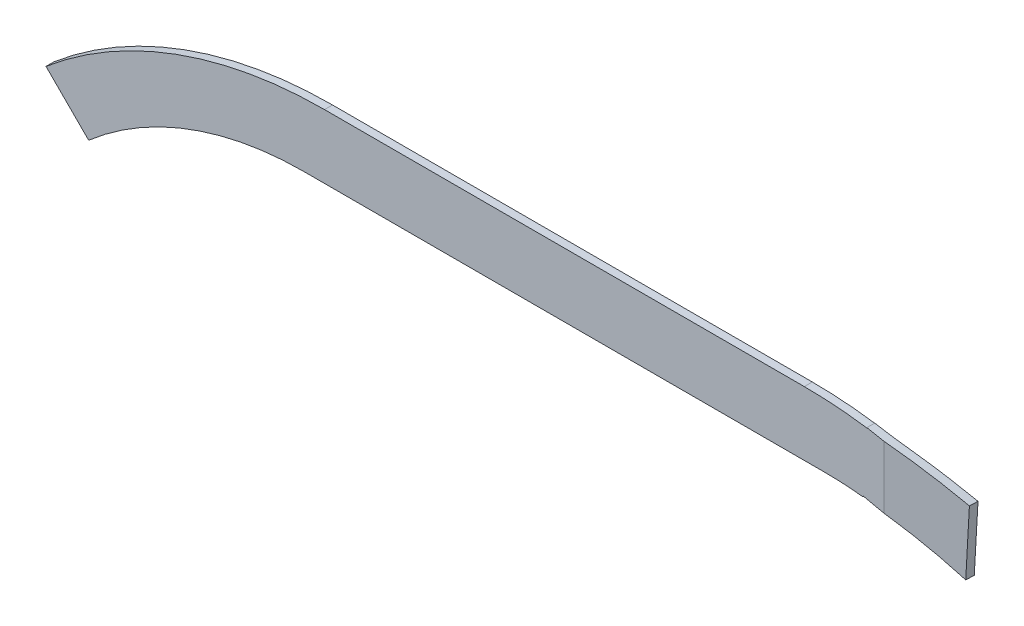
SolidWorks part; units mm, degrees
material "ABS PC"
ref_plane "Front Plane" through (0, 0, 0) normal (0, 0, 1) x (1, 0, 0)
ref_plane "Top Plane" through (0, 0, 0) normal (0, 1, 0) x (1, 0, 0)
ref_plane "Right Plane" through (0, 0, 0) normal (1, 0, 0) x (0, 0, -1)
sketch "Sketch10" plane through (0, 0, 0) normal (0, 0, 1) x (1, 0, 0)
  line L0 (37.4166, 15) -> (102.5834, 15)
  line L1 (70, -22.3542) -> (70, 54.9166) construction
  line L2 (100, 25) -> (40, 25)
  circle A0 centre (0, 0) radius 1.5
  arc A1 (4.1574, -2.7778) -> (37.4166, 15) centre (37.4166, -25) cw
  arc A2 (-4, 3) -> (40, 25) centre (40, -30) cw
  arc A3 (-4, 3) -> (4.1574, -2.7778) centre (0, 0) ccw
  arc A4 (144, 3) -> (135.8426, -2.7778) centre (140, 0) cw
  arc A5 (144, 3) -> (100, 25) centre (100, -30) ccw
  arc A6 (135.8426, -2.7778) -> (102.5834, 15) centre (102.5834, -25) ccw
  circle A7 centre (140, 0) radius 1.5
  point P8 (70, 15)
  point P21 (70, 25)
  dimension "D2" = 3
  dimension "D3" = 10
  dimension "D4" = 10
  dimension "D5" = 55
  dimension "D1" = 40
  dimension "D6" = 15
  dimension "D7" = 70
extrude "Boss-Extrude2" add sketch "Sketch10" along normal blind 18
sketch "Sketch12" plane through (0, 0, 0) normal (0, 1, 0) x (1, 0, 0)
  line L0 (-5, 0) -> (-5, -18) construction
  line L2 (-5, -6) -> (-5, -14)
  line L3 (-5, -6) -> (107.8057, -6)
  line L4 (112.2288, -5.7547) -> (125.7953, -4.2453)
  line L5 (130.2184, -4) -> (145, -4)
  line L6 (145, -18) -> (145, 0) construction
  line L7 (145, -4) -> (145, -8)
  line L8 (145, -18) -> (133.2661, -18)
  line L9 (122.9133, -16.637) -> (118.1585, -15.363)
  line L10 (107.8057, -14) -> (-5, -14)
  line L11 (100, -18) -> (144, -18) construction
  line L12 (145, -10) -> (-10.875, -10) construction
  line L16 (144, 0) -> (100, 0) construction
  line L17 (145, -8) -> (130, -8)
  line L19 (130, -14) -> (145, -14)
  line L21 (130, -8) -> (127.3597, -8.2938)
  line L23 (145, -14) -> (145, -18)
  line L27 (130, -14) -> (126.9891, -13.1932)
  arc A0 (125.7953, -4.2453) -> (130.2184, -4) centre (130.2184, -44) cw
  arc A1 (133.2661, -18) -> (122.9133, -16.637) centre (133.2661, 22) cw
  arc A2 (118.1585, -15.363) -> (107.8057, -14) centre (107.8057, -54) ccw
  arc A3 (107.8057, -6) -> (112.2288, -5.7547) centre (107.8057, 34) ccw
  circle A8 centre (76.008, -10.9313) radius 101.3633
  arc A10 (126.9891, -13.1932) -> (127.3597, -8.2938) centre (127.6362, -10.7784) cw
  point P7 (-5, -10)
  point P27 (128, -4)
  point P30 (128, -18)
  point P36 (110.024, -6)
  dimension "D10" = 40
  dimension "D18" = 2.5
  dimension "D20" = 40
  dimension "D4" = 40
  dimension "D2" = 8
  dimension "D3" = 15
  dimension "D5" = 17
  dimension "D6" = 17
  dimension "D7" = 4
  dimension "D8" = 8
  dimension "D13" = 4
  dimension "D14" = 4
  dimension "D16" = 15
  dimension "D19" = 15
extrude "Cut-Extrude1" cut sketch "Sketch12" against normal blind 21 and the other way blind 53
sketch "Sketch14" plane through (0, 0, 6) normal (0, 0, -1) x (-1, 0, 0)
  line L0 (-102.5834, 16) -> (-37.4166, 16)
  line L1 (-40, 24) -> (-100, 24)
  line L3 (-107.8191, 15.6643) -> (-107.8191, -18.7663)
  line L4 (-107.8191, 35.1683) -> (17.1624, 35.1683)
  line L5 (-107.8191, 35.1683) -> (-107.8191, 23.4309)
  line L9 (-9.7552, 5.263) -> (-4.4079, 10.6104)
  line L10 (-107.8191, -18.7663) -> (17.1624, -18.7663)
  line L11 (17.1624, 35.1683) -> (17.1624, -18.7663)
  arc A0 (-9.7552, 5.263) -> (-37.4166, 16) centre (-37.4166, -25) ccw
  arc A2 (-4.4079, 10.6104) -> (-40, 24) centre (-40, -30) ccw
  arc A3 (-100, 24) -> (-107.8191, 23.4309) centre (-100, -30) ccw
  arc A4 (-102.5834, 16) -> (-107.8191, 15.6643) centre (-102.5834, -25) ccw
extrude "Cut-Extrude2" cut sketch "Sketch14" against normal blind 4
sketch "Sketch15" plane through (2.0047, 0, 18.0182) normal (-0.1106, 0, -0.9939) x (-0.9939, 0, 0.1106)
  line L2 (-119.1631, 20.0935) -> (-118.74, 11.8221)
  line L3 (-105.9088, 23.555) -> (-106.4478, 34.0927)
  line L4 (-106.4478, 34.0927) -> (-150.1667, 16.8565)
  line L5 (-150.1667, 16.8565) -> (-142.7522, -17.5244)
  line L6 (-142.7522, -17.5244) -> (-105.9088, 7.4142)
  line L7 (-105.9088, 7.4142) -> (-105.9088, 15.8334)
  spline S2 degree 3 poles (-105.9088, 23.555) (-110.4034, 22.782) (-114.8533, 21.6192) (-119.1631, 20.0935) knots -1.323472 -1.323472 -1.323472 -1.323472 -1.15249 -1.15249 -1.15249 -1.15249
  spline S3 degree 3 poles (-118.74, 11.8221) (-114.6251, 13.6235) (-110.2967, 14.9786) (-105.9088, 15.8334) knots -1.219719 -1.219719 -1.219719 -1.219719 -0.997934 -0.997934 -0.997934 -0.997934
extrude "Cut-Extrude3" cut sketch "Sketch15" against normal blind 4 and the other way blind 4
sketch "Sketch16" plane through (0, 24, 0) normal (0, 1, 0) x (1, 0, 0)
  line L0 (100, -6) -> (40, -6) construction
  line L1 (3.4079, -7) -> (109.9429, -7)
  line L3 (3.4079, -30.8831) -> (117.671, -30.8831)
  line L4 (117.671, -29.7878) -> (117.671, -30.8831)
  line L6 (109.9429, -7) -> (121.047, -5.8637)
  line L8 (4.4079, -10) -> (4.4079, -6) construction
  line L9 (3.4079, -7) -> (3.4079, -0.6919)
  line L10 (3.4079, -0.6919) -> (-16.2394, -3.1241)
  line L11 (-16.2394, -3.1241) -> (-7.7296, -28.6925)
  line L12 (-7.7296, -28.6925) -> (3.4079, -30.8831)
  line L13 (121.047, -5.8637) -> (121.047, -0.4541)
  line L14 (121.047, -0.4541) -> (147.2791, 4.0786)
  line L15 (147.2791, 4.0786) -> (150.0769, -41.0169)
  line L16 (150.0769, -41.0169) -> (122.1049, -29.7878)
  line L17 (122.1049, -29.7878) -> (117.671, -29.7878)
  dimension "D1" = 1
  dimension "D2" = 1
extrude "Cut-Extrude4" cut sketch "Sketch16" against normal through all both and the other way through all
sketch "Sketch17" plane through (0, 0, 6) normal (0, 0, -1) x (-1, 0, 0)
  line L0 (-4.3327, 12.0998) -> (-11.6654, 4.7671)
  line L1 (-4.4079, 10.6104) -> (-9.7552, 5.263) construction
  line L2 (-4.3327, 12.0998) -> (-1.1342, 10.2513)
  line L3 (-1.1342, 10.2513) -> (-10.5936, 3.6954)
  line L4 (-10.5936, 3.6954) -> (-11.583, 4.6848)
  line L5 (-11.583, 4.6848) -> (-11.6654, 4.7671)
  line L6 (-119.7131, 21.6104) -> (-119.1112, 9.7702)
  line L7 (-120.0165, 11.8221) -> (-120.437, 20.0935) construction
  line L8 (-119.7131, 21.6104) -> (-122.5692, 21.0391)
  line L9 (-122.5692, 21.0391) -> (-121.8891, 7.6605)
  line L10 (-121.8891, 7.6605) -> (-119.1112, 9.7702)
  dimension "D1" = 1
  dimension "D2" = 0.8
extrude "Cut-Extrude5" cut sketch "Sketch17" against normal through all both and the other way through all
